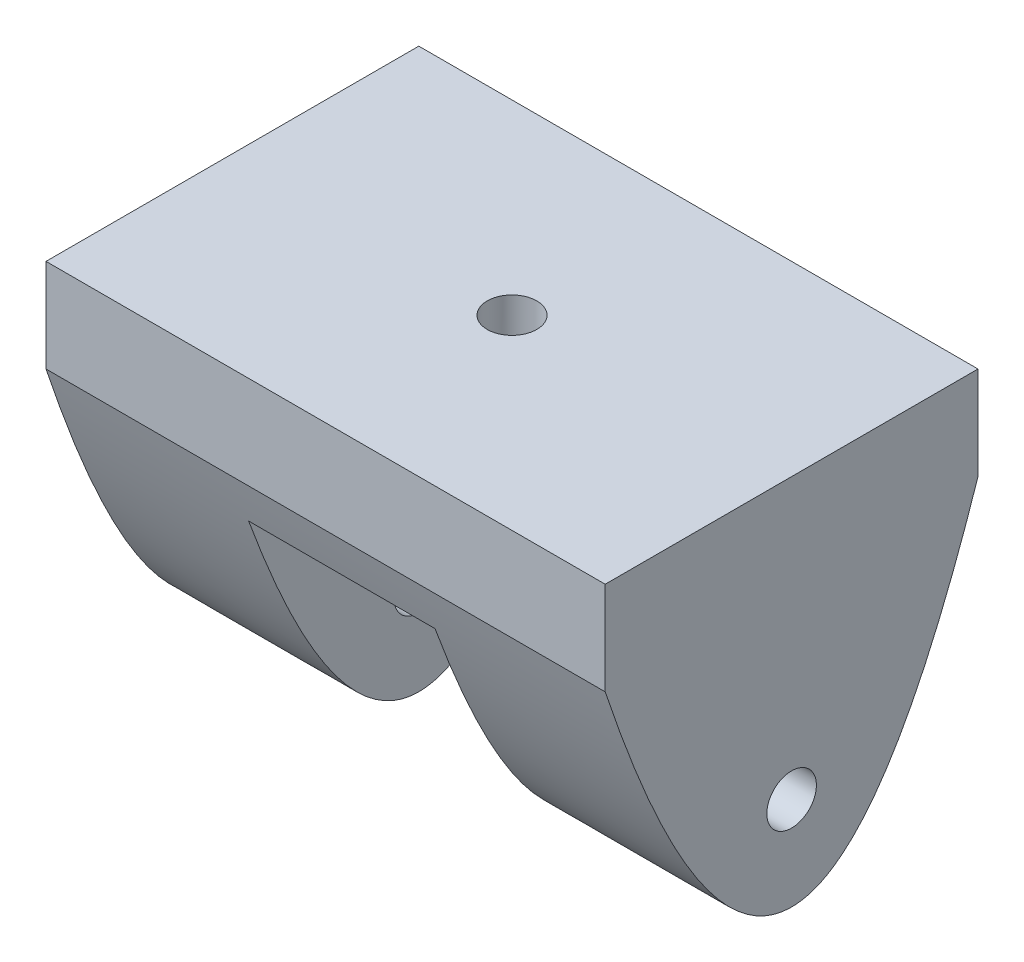
SolidWorks part; units mm, degrees
ref_plane "Front Plane" through (0, 0, 0) normal (0, 0, 1) x (1, 0, 0)
ref_plane "Top Plane" through (0, 0, 0) normal (0, 1, 0) x (1, 0, 0)
ref_plane "Right Plane" through (0, 0, 0) normal (1, 0, 0) x (0, 0, -1)
sketch "Sketch1" plane through (0, 0, 0) normal (0, 1, 0) x (1, 0, 0)
  line L0 (-12.7, 25.4) -> (-12.7, -25.4)
  line L1 (-38.1, 25.4) -> (38.1, 25.4)
  line L2 (-38.1, 25.4) -> (-38.1, -25.4)
  line L3 (-38.1, -25.4) -> (38.1, -25.4)
  line L4 (38.1, 25.4) -> (38.1, -25.4)
  line L5 (-38.1, 25.4) -> (38.1, -25.4) construction
  line L6 (-38.1, -25.4) -> (38.1, 25.4) construction
  line L7 (12.7, 25.4) -> (12.7, -25.4)
  dimension "D1" = 50.8
  dimension "D2" = 76.2
  dimension "D4" = 25.4
  dimension "D5" = 25.4
extrude "Boss-Extrude1" add sketch "Sketch1" along normal blind 19.05 contours L7 L1 L0 L3 | L1 L7 L3 L4 | L2 L3 L0 L1 region at (0, 0, 0) region at (-25.4, 0, 0) region at (25.4, 0, 0)
extrude "Boss-Extrude3" add sketch "Sketch1<7>" against normal blind 44.45 contours L2 L3 L0 L1 | L1 L7 L3 L4 region at (-25.4, 0, 0) region at (25.4, 0, 0)
sketch "Sketch1<7>" plane through (0, 0, 0) normal (0, 1, 0) x (1, 0, 0) same geometry as "Sketch1"
sketch "Sketch2" plane through (-38.1, 0, 0) normal (-1, 0, 0) x (0, 0, 1)
  line L0 (-25.4, -44.45) -> (25.4, -44.45) construction
  line L1 (0, 19.05) -> (0, -44.45) construction
  line L2 (-25.4, 19.05) -> (25.4, 19.05) construction
  line L3 (25.4, 19.05) -> (25.4, -44.45) construction
  line L4 (-25.4, 19.05) -> (-25.4, -44.45) construction
  circle A0 centre (0, -19.05) radius 3.3782
  spline S0 degree 2 poles (25.4, 6.35) (0, -69.85) (-25.4, 6.35) knots 0 0 0 1 1 1
  point P10 (0, -34.3592)
  point P12 (25.4, 0)
  point P13 (0, 0)
  point P18 (0, 0)
  line M3 (-25.4, 19.05) -> (-25.4, -44.45)
  line M4 (-25.4, -44.45) -> (25.4, -44.45)
  line M5 (25.4, -44.45) -> (25.4, 19.05)
  dimension "D2" = 6.7564
  dimension "D1" = 25.4
  dimension "D3" = 12.7
  dimension "D4" = 12.7
extrude "Cut-Extrude4" cut sketch "Sketch2" against normal through all contours L1 A0 | A0 L1 | L1 S0 M3 M4 | S0 L1 M4 M5 region at (-38.1, -19.05, 1.4338) region at (-38.1, -29.21, 15.875) region at (-38.1, -29.21, -15.875) region at (-38.1, -19.05, -1.4338)
sketch "Sketch3" plane through (0, 19.05, 0) normal (0, 1, 0) x (1, 0, 0)
  circle A0 centre (0, 0) radius 3.3782
  dimension "D1" = 6.7564
extrude "Cut-Extrude5" cut sketch "Sketch3" against normal through all
ref_plane "Plane2" through (0, 9.525, 0) normal (0, -1, 0) x (-1, 0, 0)
sketch "Sketch4" plane through (0, 9.525, 0) normal (0, -1, 0) x (-1, 0, 0)
  line L0 (-12.7, -23.1869) -> (12.7, -23.1869) construction
  line L1 (3.2996, -5.715) -> (6.5991, 0)
  line L2 (6.5991, 0) -> (3.2996, 5.715)
  line L3 (3.2996, 5.715) -> (-3.2996, 5.715)
  line L4 (-3.2996, 5.715) -> (-6.5991, 0)
  line L5 (-6.5991, 0) -> (-3.2996, -5.715)
  line L6 (-3.2996, -5.715) -> (3.2996, -5.715)
  line L7 (6.5991, 0) -> (6.5991, 25.4)
  line L8 (6.5991, 25.4) -> (-6.5991, 25.4)
  line L9 (-6.5991, 25.4) -> (-6.5991, 0)
  line L10 (-38.1, 25.4) -> (38.1, 25.4) construction
  circle A0 centre (0, 0) radius 5.715 construction
  point P11 (0, 0)
  point P14 (0, 0)
  dimension "D1" = 11.43
extrude "Cut-Extrude6" cut sketch "Sketch4" against normal mid plane 8.89 contours L8 L9 L4 L3 L2 L7 | L5 L6 L1 L2 L3 L4 region at (0, 9.525, 0) region at (0, 9.525, -14.7626)
